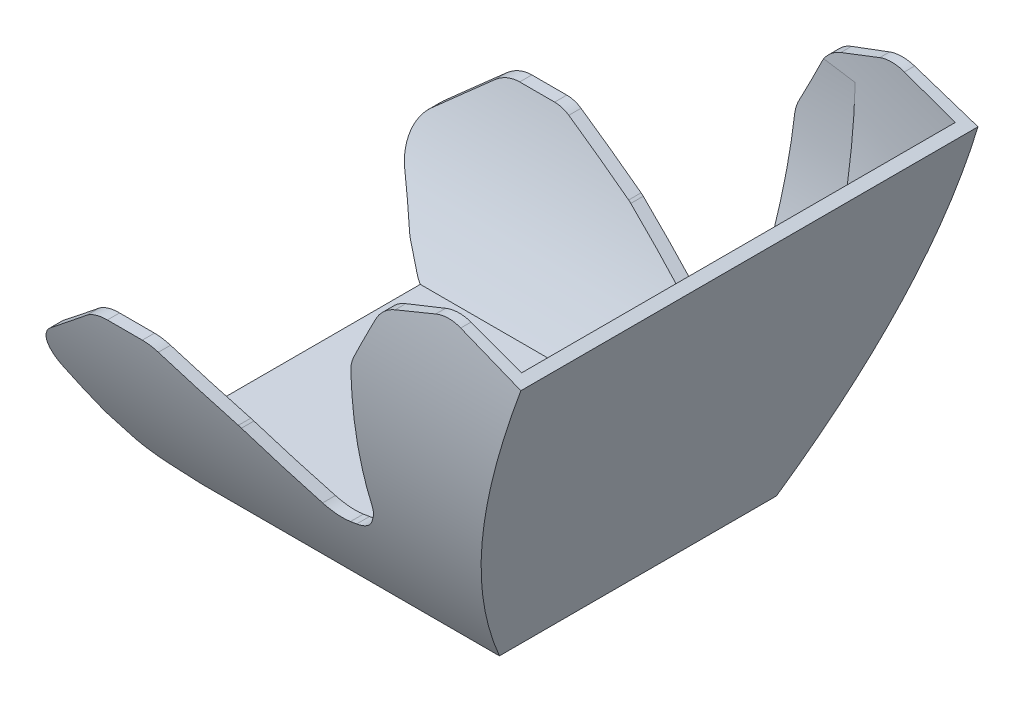
SolidWorks part; units mm, degrees
material "PET"
ref_plane "Ön Düzlem" through (0, 0, 0) normal (0, 0, 1) x (1, 0, 0)
ref_plane "Üst Düzlem" through (0, 0, 0) normal (0, 1, 0) x (1, 0, 0)
ref_plane "Sağ Düzlem" through (0, 0, 0) normal (1, 0, 0) x (0, 0, -1)
sketch "Çizim2" plane through (0, 0, 0) normal (0, 0, 1) x (1, 0, 0)
  line L0 (-251.5983, 0) -> (0, 0)
  line L1 (0, 0) -> (94.7709, 280.8709)
  line L2 (94.7709, 280.8709) -> (42.2716, 300.0378)
  line L3 (21.026, 299.7846) -> (-12.4412, 286.6539)
  line L4 (-28.2694, 272.2375) -> (-47.2684, 234.5721)
  line L5 (-50.4474, 222.524) -> (-55.9904, 108.9866)
  line L6 (-59.7325, 95.8756) -> (-62.5121, 90.8744)
  line L7 (-81.4591, 76.3438) -> (-87.335, 74.875)
  line L8 (-109.7191, 78.0619) -> (-166.2357, 111.0088)
  line L9 (-168.4809, 112.1933) -> (-227.9999, 140.4434)
  line L10 (-240.8641, 143.3413) -> (-270.545, 143.3407)
  line L11 (-290.0273, 136.1534) -> (-332.2462, 100.0969)
  line L12 (-337.8976, 60.9053) -> (-319.1537, 32.1421)
  line L13 (-315.4731, 27.551) -> (-302.6843, 14.4673)
  line L14 (-292.2676, 7.5413) -> (-287.3376, 5.5908)
  line L15 (-280.4937, 3.7812) -> (-255.7913, 0.2945)
  line L16 (0, 0) -> (250.42, 0) construction
  arc A0 (-251.5983, 0) -> (-255.7913, 0.2945) centre (-251.5983, 30) cw
  arc A1 (-287.3376, 5.5908) -> (-280.4937, 3.7812) centre (-276.3007, 33.4868) ccw
  arc A2 (-302.6843, 14.4673) -> (-292.2676, 7.5413) centre (-281.2307, 35.4373) ccw
  arc A3 (-319.1537, 32.1421) -> (-315.4731, 27.551) centre (-294.0195, 48.521) ccw
  arc A4 (-332.2462, 100.0969) -> (-337.8976, 60.9053) centre (-312.7633, 77.2842) ccw
  arc A5 (-270.545, 143.3407) -> (-290.0273, 136.1534) centre (-270.5444, 113.3407) ccw
  arc A6 (-227.9999, 140.4434) -> (-240.8641, 143.3413) centre (-240.8636, 113.3413) ccw
  arc A7 (-166.2357, 111.0088) -> (-168.4809, 112.1933) centre (-181.3446, 85.0912) ccw
  arc A8 (-87.335, 74.875) -> (-109.7191, 78.0619) centre (-94.6102, 103.9795) cw
  arc A9 (-62.5121, 90.8744) -> (-81.4591, 76.3438) centre (-88.7343, 105.4483) cw
  arc A10 (-55.9904, 108.9866) -> (-59.7325, 95.8756) centre (-85.9547, 110.4494) cw
  arc A11 (-47.2684, 234.5721) -> (-50.4474, 222.524) centre (-20.4831, 221.0611) ccw
  arc A12 (-12.4412, 286.6539) -> (-28.2694, 272.2375) centre (-1.4841, 258.7265) ccw
  arc A13 (42.2716, 300.0378) -> (21.026, 299.7846) centre (31.9831, 271.8572) ccw
  dimension "D1" = 30
  dimension "D2" = 71.355
extrude "Yükseklik-Ekstrüzyon1" add sketch "Çizim2" along normal mid plane 500 from offset 0 contours L5 A10 L6 A9 L7 A8 L8 A7 L9 A6 L10 A5 L11 A4 L12 A3 L13 A2 L14 A1 L15 A0 L0 L1 L2 A13 L3 A12 L4 A11
sketch "Çizim13" plane through (0, 0, 0) normal (1, 0, 0) x (0, 0, -1)
  line L0 (-250, 0) -> (250, 0) construction
  line L1 (250, 0) -> (250, 415.9485) construction
  line L2 (250, 415.9485) -> (-250, 415.9485) construction
  line L3 (-250, 415.9485) -> (-250, 0) construction
  line L4 (0, 0) -> (0, -83.3442) construction
  line L5 (-169.0199, 378.3058) -> (169.0199, 378.3058)
  line L6 (-117.7174, 0) -> (117.7174, 0)
  line L7 (-176.716, 388.3058) -> (176.716, 388.3058)
  line L8 (-112.1336, 10) -> (112.1336, 10)
  line L9 (-269.8869, 462.4979) -> (294.8817, 462.4979)
  line L10 (294.8817, 462.4979) -> (294.8817, -53.8187)
  line L11 (294.8817, -53.8187) -> (-294.1129, -53.8187)
  line L12 (-294.1129, -53.8187) -> (-269.8869, 462.4979)
  spline S0 degree 3 poles (-176.716, 388.3058) (-213.7904, 252.1367) (-194.1242, 122.7015) (-117.7174, 0) knots 0.063182 0.063182 0.063182 0.063182 1 1 1 1
  spline S1 degree 3 poles (176.716, 388.3058) (213.7904, 252.1367) (194.1242, 122.7015) (117.7174, 0) knots 0.063182 0.063182 0.063182 0.063182 1 1 1 1
  spline S2 degree 1 poles (169.0199, 378.3058) (112.1336, 10) knots 0 0 1 1 construction
  spline S3 degree 1 poles (-169.0199, 378.3058) (-112.1336, 10) knots 0 0 1 1 construction
  spline S4 degree 3 poles (169.0199, 378.3058) (170.055, 374.2845) (172.0392, 366.1915) (175.5803, 350.1293) (179.2447, 330.1331) (182.4133, 306.3128) (184.3589, 282.6522) (185.0825, 259.1511) (184.4199, 228.0226) (180.5426, 189.4889) (172.5982, 151.4277) (163.7958, 121.2464) (155.968, 98.741) (146.9116, 76.3633) (138.3382, 57.8201) (130.8621, 43.0474) (124.9463, 31.9996) (119.7574, 22.8166) (115.4543, 15.4904) (113.2458, 11.8238) (112.1336, 10) knots 0.080413 0.080413 0.080413 0.080413 0.108769 0.137126 0.193838 0.25055 0.307262 0.363974 0.420687 0.534111 0.647536 0.704248 0.76096 0.817672 0.874384 0.902741 0.931097 0.959453 0.973631 0.987809 0.987809 0.987809 0.987809
  spline S5 degree 3 poles (-112.1336, 10) (-113.2458, 11.8238) (-115.4543, 15.4904) (-119.7574, 22.8166) (-124.9463, 31.9996) (-130.8621, 43.0474) (-138.3382, 57.8201) (-146.9116, 76.3633) (-155.968, 98.741) (-163.7958, 121.2464) (-172.5982, 151.4277) (-180.5426, 189.4889) (-184.4199, 228.0226) (-185.0825, 259.1511) (-184.3589, 282.6522) (-182.4133, 306.3128) (-179.2447, 330.1331) (-175.5803, 350.1293) (-172.0392, 366.1915) (-170.055, 374.2845) (-169.0199, 378.3058) knots 0.080413 0.080413 0.080413 0.080413 0.094591 0.108769 0.137126 0.165482 0.193838 0.25055 0.307262 0.363974 0.420687 0.534111 0.647536 0.704248 0.76096 0.817672 0.874384 0.931097 0.959453 0.987809 0.987809 0.987809 0.987809
  dimension "D1" = 10
extrude "Kes-Ekstrüzyon13" cut sketch "Çizim13" against normal mid plane 1000 contours L12 L11 L10 L9 L7 S1 L6 S0 region at (0, 454.6653, -12.4974)
extrude "Kes-Ekstrüzyon14" cut sketch "Çizim13<3>" against normal blind 1000 contours S5 L8 S4 L5 region at (0, 204.3051, 0)
sketch "Çizim13<3>" plane through (0, 0, 0) normal (1, 0, 0) x (0, 0, -1) same geometry as "Çizim13"
sketch "Çizim14" plane through (0, 0, 0) normal (0.9475, -0.3197, 0) x (0, 0, -1)
  line L2 (-180.1496, 340.7465) -> (180.1484, 340.7465)
  line L4 (-111.9771, 10) -> (111.9771, 10)
  line L5 (184.6551, 286.4287) -> (-184.6551, 286.4287)
  line L6 (-111.9771, 10) -> (111.9771, 10)
  spline S4 degree 3 poles (2972.4278, 2619.3391) (1367.4763, 1789.702) (-268.3591, 958.5094) (-180.8765, 208.0674) (-180.0634, 202.0631) (-178.2192, 190.1132) (-175.1242, 172.2594) (-170.3745, 151.6762) (-166.3174, 137.1177) (-164.6416, 131.3057) (-163.7768, 128.4038) (-161.1078, 119.7295) (-159.2297, 113.9898) (-153.3082, 96.8966) (-148.9779, 85.6686) (193.1465, -721.7328) (2392.875, -702.9832) (-699.3975, -3000.4122) knots -7.495288 -7.495288 -7.495288 -7.495288 0.25 0.25 0.3125 0.3125 0.375 0.5 0.53125 0.53125 0.5625 0.5625 0.625 0.625 0.75 0.75 9.741824 9.741824 9.741824 9.741824 only from (-184.6551, 286.4287) to (-111.9771, 10)
  spline S5 degree 3 poles (966.1283, -3044.5536) (-2106.2162, -628.8603) (-172.6806, -674.3966) (146.7439, 80.4039) (149.0127, 86.0214) (153.3513, 97.3106) (159.5663, 114.3384) (164.8852, 131.6534) (168.7993, 146.2488) (169.5562, 149.1762) (171.0177, 155.0478) (171.7226, 157.9939) (173.7542, 166.8407) (177.4852, 184.5678) (180.2214, 202.3951) (256.2701, 857.6794) (-948.1731, 1629.8782) (-3042.5997, 2491.7244) knots -8.154919 -8.154919 -8.154919 -8.154919 0.25 0.25 0.3125 0.3125 0.375 0.5 0.5 0.53125 0.53125 0.5625 0.5625 0.625 0.75 0.75 7.49142 7.49142 7.49142 7.49142 only from (111.9771, 10) to (184.6551, 286.4287)
  spline S6 degree 3 poles (-180.1496, 340.7465) (-185.8872, 298.2575) (-186.4676, 256.0283) (-180.8765, 208.0674) (-180.0634, 202.0631) (-178.2192, 190.1132) (-175.1242, 172.2594) (-170.3745, 151.6762) (-166.3174, 137.1177) (-164.6416, 131.3057) (-163.7768, 128.4038) (-161.1078, 119.7295) (-159.2297, 113.9898) (-153.3082, 96.8966) (-148.9779, 85.6686) (-134.9054, 52.4579) (-124.0841, 30.9476) (-111.9771, 10) knots -0.186497 -0.186497 -0.186497 -0.186497 0.25 0.25 0.3125 0.3125 0.375 0.5 0.53125 0.53125 0.5625 0.5625 0.625 0.625 0.75 0.75 1 1 1 1
  spline S7 degree 3 poles (111.9771, 10) (124.0941, 30.9648) (134.9552, 52.5471) (146.7439, 80.4039) (149.0127, 86.0214) (153.3513, 97.3106) (159.5663, 114.3384) (164.8852, 131.6534) (168.7993, 146.2488) (169.5562, 149.1762) (171.0177, 155.0478) (171.7226, 157.9939) (173.7542, 166.8407) (177.4852, 184.5678) (180.2214, 202.3951) (186.4344, 255.9297) (185.9134, 298.074) (180.1484, 340.7465) knots 0 0 0 0 0.25 0.25 0.3125 0.3125 0.375 0.5 0.5 0.53125 0.53125 0.5625 0.5625 0.625 0.75 0.75 1.185964 1.185964 1.185964 1.185964
  dimension "D1" = 10
sketch "Çizim15" plane through (0, 0, 0) normal (0, -1, 0) x (1, 0, 0)
  line L0 (0, 0) -> (-506.6376, 0) construction
  line L1 (-138.3969, 70) -> (-138.3969, -70) construction
  circle A0 centre (-138.3969, 70) radius 5
  circle A1 centre (-38.3969, 70) radius 5
  circle A2 centre (-38.3969, -70) radius 5
  circle A3 centre (-138.3969, -70) radius 5
extrude "Yükseklik-Ekstrüzyon4" add sketch "Çizim15" along normal blind 8
extrude "Kes-Ekstrüzyon16" cut sketch "Çizim14" against normal blind 398 from offset 10 offset against normal yes
